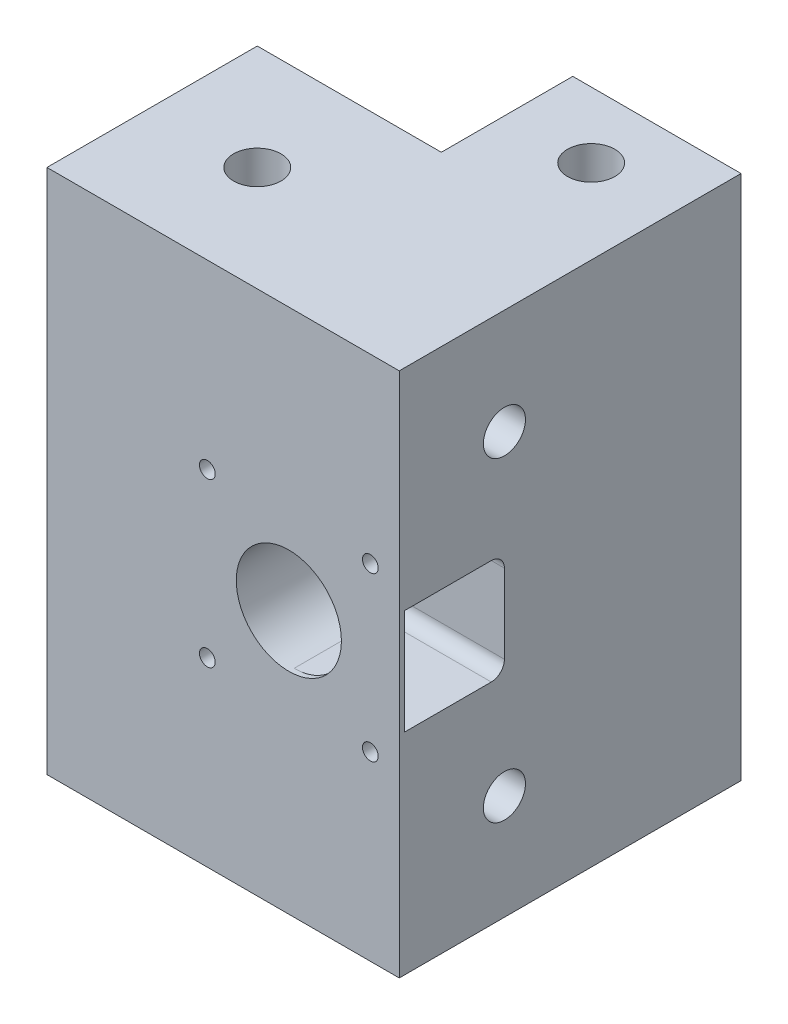
SolidWorks part; units mm, degrees
ref_plane "Front Plane" through (0, 0, 0) normal (0, 0, 1) x (1, 0, 0)
ref_plane "Top Plane" through (0, 0, 0) normal (0, 1, 0) x (1, 0, 0)
ref_plane "Right Plane" through (0, 0, 0) normal (1, 0, 0) x (0, 0, -1)
sketch "Sketch1" plane through (0, 0, 0) normal (0, 1, 0) x (1, 0, 0)
  line L19 (0, -40) -> (0, 0) construction
  line L24 (-25, 0) -> (-5, -40) construction
  line L25 (0, 25) -> (-25, 25) construction
  line L26 (-25, 25) -> (-25, 0) construction
  line L27 (0, 25) -> (32, 0) construction
  line L28 (32, 0) -> (0, 0) construction
  line L29 (-35, 0) -> (0, 0)
  line L30 (-35, -40) -> (-35, 0)
  line L31 (32, -40) -> (-35, -40)
  line L32 (32, 25) -> (32, -40)
  line L33 (0, 25) -> (32, 25)
  line L34 (0, 0) -> (0, 25)
  line L35 (-5, 5) -> (-5, -40) construction
  line L36 (-25, 25) -> (-5, 25) construction
  line L37 (-25, 25) -> (-25, 5) construction
  line L38 (-25, 5) -> (-5, 5) construction
  line L39 (-5, 25) -> (-5, 5) construction
  line L40 (16, 12.5) -> (-5, 22.5) construction
  line L41 (-25, 2.5) -> (-5, 2.5) construction
  line L42 (-25, 2.5) -> (-25, 22.5) construction
  line L43 (-25, 22.5) -> (-5, 22.5) construction
  line L44 (-5, 2.5) -> (-5, 22.5) construction
  line L45 (-25, 2.5) -> (-5, 22.5) construction
  line L46 (-25, 22.5) -> (-5, 2.5) construction
  line L47 (16, 12.5) -> (-5, 2.5) construction
  circle A10 centre (-15, -20) radius 16 construction
  circle A11 centre (-15, -20) radius 6.75 construction
  circle A12 centre (16, 12.5) radius 6 construction
  circle A13 centre (16, 12.5) radius 11 construction
  circle A14 centre (-15, -20) radius 4.5
  circle A15 centre (16, 12.5) radius 4.5
  point P1 (-15, 12.5)
  dimension "D4" = 40
  dimension "D6" = 9
  dimension "D3" = 32
  dimension "D5" = 20
  dimension "D7" = 13.5
  dimension "D8" = 32
  dimension "D9" = 9
  dimension "D10" = 12
  dimension "D11" = 22
  dimension "D1" = 25
  dimension "D2" = 25
  dimension "D12" = 20
extrude "Boss-Extrude1" add sketch "Sketch1" along normal blind 100
sketch "Sketch4" plane through (0, 0, 0) normal (0, -1, 0) x (-1, 0, 0)
  point P0 (15, -20)
hole_wizard "CBORE for M5 Hex Head Bolt2" positions "Sketch4" profile "Sketch5" counterbore size "M5" standard "ANSI Metric"
sketch "Sketch5" plane through (-15, 0, 20) normal (1, 0, 0) x (0, 0, -1)
  line L0 (0, 0) -> (0, 23.85)
  line L1 (0, 23.85) -> (6.75, 23.85)
  line L2 (6.75, 23.85) -> (6.75, 5)
  line L3 (6.75, 5) -> (16, 5)
  line L4 (16, 5) -> (16, 0)
  line L5 (16, 0) -> (0, 0)
  line L10 (0, 23.85) -> (-6.75, 23.85) construction
  line L11 (0, -6.35) -> (0, 107.95) construction
  dimension "Hole Dia." = 13.5
  dimension "Hole Depth" = 23.85
  dimension "C'Bore Dia." = 32
  dimension "C'Bore Depth" = 5
  dimension "Drill Angle" = 180
sketch "Sketch6" plane through (0, 0, 0) normal (0, -1, 0) x (-1, 0, 0)
  point P0 (-16, 12.5)
hole_wizard "CBORE for M5 Hex Head Bolt3" positions "Sketch6" profile "Sketch7" counterbore size "M5" standard "ANSI Metric"
sketch "Sketch7" plane through (16, 0, -12.5) normal (1, 0, 0) x (0, 0, -1)
  line L0 (0, 0) -> (0, 13.5)
  line L1 (0, 13.5) -> (5.1, 13.5)
  line L2 (5.1, 13.5) -> (5.1, 3.5)
  line L3 (5.1, 3.5) -> (11, 3.5)
  line L4 (11, 3.5) -> (11, 0)
  line L5 (11, 0) -> (0, 0)
  line L10 (0, 13.5) -> (-5.1, 13.5) construction
  line L11 (0, -6.35) -> (0, 107.95) construction
  dimension "Hole Dia." = 10.2
  dimension "Hole Depth" = 13.5
  dimension "C'Bore Dia." = 22
  dimension "C'Bore Depth" = 3.5
  dimension "Drill Angle" = 180
sketch "Sketch8" plane through (32, 0, 0) normal (1, 0, 0) x (0, 0, -1)
  line L0 (0, 100) -> (0, 0) construction
  line L1 (-40, 100) -> (25, 100) construction
  line L2 (0, 100) -> (-40, 0) construction
  line L3 (-40, 100) -> (-40, 0) construction
  line L4 (-40, 0) -> (25, 0) construction
  line L5 (-20, 100) -> (-20, 0) construction
  circle A0 centre (-20, 80) radius 4
  circle A1 centre (-20, 20) radius 4
  point P12 (-20, 50)
  point P17 (-20, 21.4284)
  point P18 (0, 0)
  dimension "D1" = 8
  dimension "D2" = 60
  dimension "D3" = 30
extrude "Cut-Extrude1" cut sketch "Sketch8" against normal blind 27
sketch "Sketch9" plane through (0, 0, 40) normal (0, 0, 1) x (1, 0, 0)
  line L0 (-10, 100) -> (-10, 0) construction
  line L2 (-35, 100) -> (32, 100) construction
  line L3 (-35, 0) -> (32, 0) construction
  line L4 (-4.5, 34.5) -> (26.5, 34.5) construction
  line L5 (32, 100) -> (32, 0) construction
  line L6 (32, 100) -> (-10, 0) construction
  line L7 (-4.5, 34.5) -> (-4.5, 65.5) construction
  line L8 (-4.5, 65.5) -> (26.5, 65.5) construction
  line L9 (26.5, 34.5) -> (26.5, 65.5) construction
  line L10 (-4.5, 34.5) -> (26.5, 65.5) construction
  line L11 (-4.5, 65.5) -> (26.5, 34.5) construction
  circle A0 centre (-4.5, 65.5) radius 1.5
  circle A1 centre (26.5, 65.5) radius 1.5
  circle A2 centre (26.5, 34.5) radius 1.5
  circle A3 centre (-4.5, 34.5) radius 1.5
  point P4 (11, 50)
  point P16 (0, 0)
  point P17 (0, 0)
  dimension "D3" = 3
  dimension "D1" = 42
  dimension "D2" = 31
  dimension "D4" = 2
  dimension "D5" = 2
extrude "Cut-Extrude2" cut sketch "Sketch9" against normal blind 119
sketch "Sketch10" plane through (0, 0, 40) normal (0, 0, 1) x (1, 0, 0)
  line L0 (-4.5, 65.5) -> (26.5, 65.5) construction
  line L1 (26.5, 65.5) -> (26.5, 34.5) construction
  line L2 (26.5, 34.5) -> (-4.5, 34.5) construction
  line L3 (-4.5, 34.5) -> (-4.5, 65.5) construction
  line L4 (-4.5, 65.5) -> (26.5, 34.5) construction
  line L5 (26.5, 65.5) -> (-4.5, 34.5) construction
  circle A0 centre (11, 50) radius 10
  dimension "D1" = 20
sketch "Sketch11" plane through (32, 0, 0) normal (1, 0, 0) x (0, 0, -1)
  line L0 (-20, 80) -> (-20, 20) construction
  line L1 (-20, 50) -> (-40, 50) construction
  line L2 (-39, 40) -> (-20, 40)
  line L3 (-39, 40) -> (-39, 60)
  line L4 (-39, 60) -> (-20, 60)
  line L5 (-20, 40) -> (-20, 60)
  line L6 (-39, 40) -> (-20, 60) construction
  line L7 (-39, 60) -> (-20, 40) construction
  line L9 (-40, 60) -> (-40, 40) construction
  line L10 (-40, 65.5) -> (-40, 34.5) construction
  point P4 (-20, 50)
  point P13 (-29.5, 50)
  point P14 (0, 0)
  point P15 (0, 0)
  point P16 (0, 0)
  dimension "D1" = 20
  dimension "D2" = 20
  dimension "D3" = 1
extrude "Cut-Extrude3" cut sketch "Sketch10" against normal blind 20 contours A0
extrude "Cut-Extrude4" cut sketch "Sketch11" against normal blind 21
fillet "Fillet2" radius 2.5 3 edges at (21.5, 40, 20) (1, 50, 20) (21.5, 60, 20)
